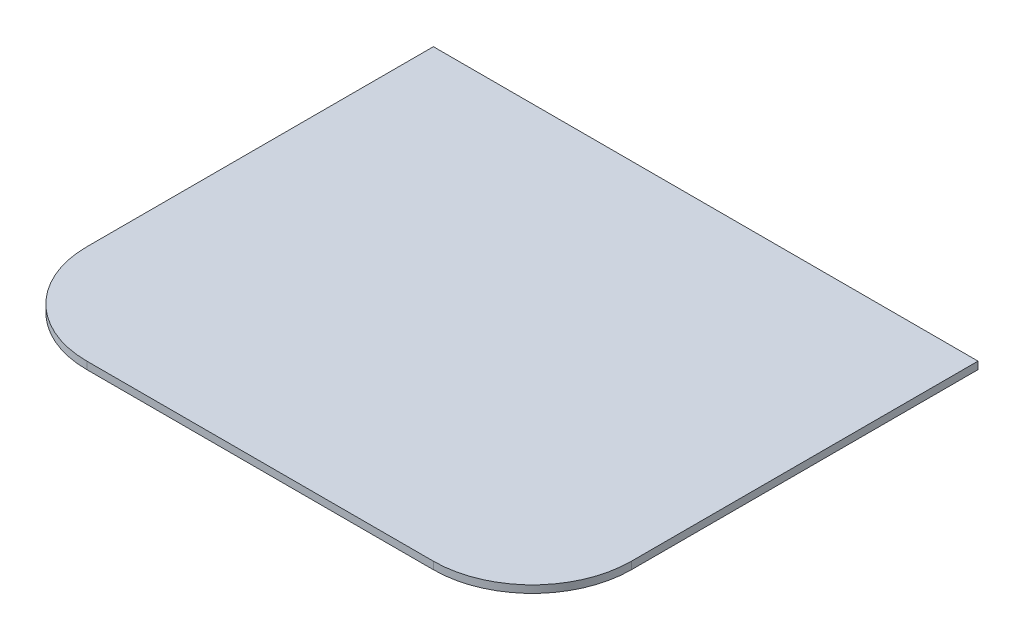
SolidWorks part; units mm, degrees
ref_plane "Front Plane" through (0, 0, 0) normal (0, 0, 1) x (1, 0, 0)
ref_plane "Top Plane" through (0, 0, 0) normal (0, 1, 0) x (1, 0, 0)
ref_plane "Right Plane" through (0, 0, 0) normal (1, 0, 0) x (0, 0, -1)
sketch "Sketch2" plane through (0, 0, 0) normal (0, 1, 0) x (1, 0, 0)
  line L3 (110, 90) -> (-110, 90)
  line L4 (110, 90) -> (110, -90)
  line L5 (110, -90) -> (-110, -90)
  line L6 (-110, 90) -> (-110, -90)
  line L7 (110, 90) -> (-110, -90) construction
  line L8 (110, -90) -> (-110, 90) construction
  point P0 (0, 0)
  dimension "D1" = 220
  dimension "D2" = 180
extrude "Boss-Extrude1" add sketch "Sketch2" along normal blind 3
fillet "Fillet1" radius 40 2 edges at (-110, 1.5, 90) (110, 1.5, 90)
